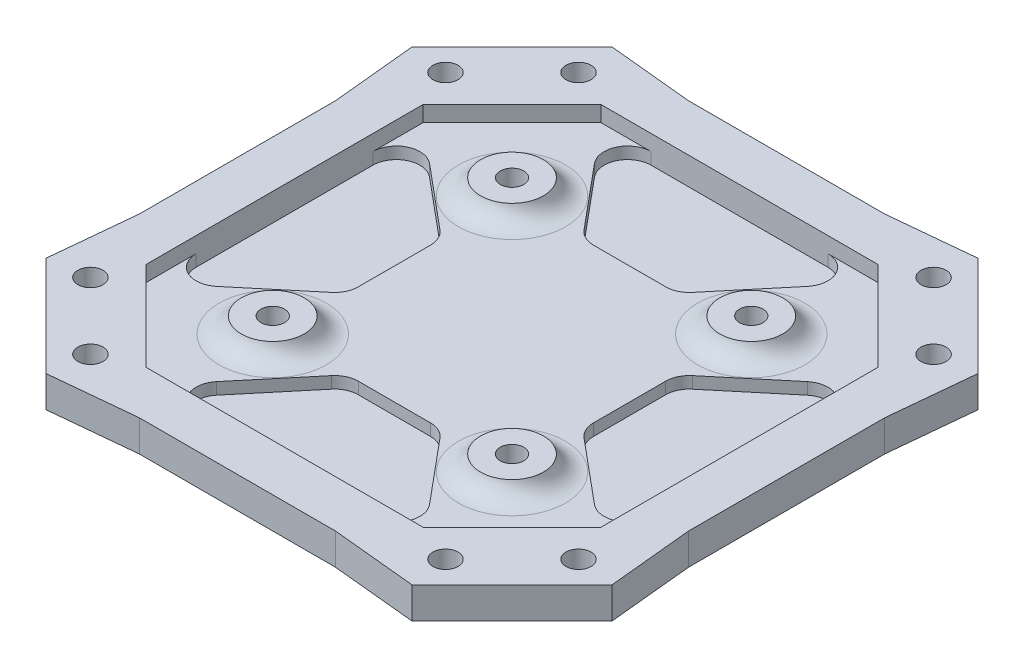
SolidWorks part; units mm, degrees
ref_plane "Front Plane" through (0, 0, 0) normal (0, 0, 1) x (1, 0, 0)
ref_plane "Top Plane" through (0, 0, 0) normal (0, 1, 0) x (1, 0, 0)
ref_plane "Right Plane" through (0, 0, 0) normal (1, 0, 0) x (0, 0, -1)
sketch "Sketch1" plane through (0, 0, 0) normal (0, 1, 0) x (1, 0, 0)
  line L0 (-12.5, 0) -> (12.5, 0)
  line L1 (12.5, 0) -> (23.338, 1.0627)
  line L2 (23.338, 1.0627) -> (36.0659, -11.6652)
  line L3 (36.0659, -11.6652) -> (35.0033, -22.5033)
  line L4 (35.0033, -22.5033) -> (35.0033, -47.5033)
  line L5 (0, 0) -> (0, -59.9756) construction
  line L6 (35.0033, -35.0033) -> (-52.1457, -35.0033) construction
  line L7 (-35.0033, -22.5033) -> (-35.0033, -47.5033)
  line L8 (-36.0659, -11.6652) -> (-35.0033, -22.5033)
  line L9 (-23.338, 1.0627) -> (-36.0659, -11.6652)
  line L10 (-12.5, 0) -> (-23.338, 1.0627)
  line L11 (0, -70.0065) -> (0, -10.0309) construction
  line L12 (-12.5, -70.0065) -> (-23.338, -71.0692)
  line L13 (-23.338, -71.0692) -> (-36.0659, -58.3413)
  line L14 (-36.0659, -58.3413) -> (-35.0033, -47.5033)
  line L15 (36.0659, -58.3413) -> (35.0033, -47.5033)
  line L16 (23.338, -71.0692) -> (36.0659, -58.3413)
  line L17 (12.5, -70.0065) -> (23.338, -71.0692)
  line L18 (-12.5, -70.0065) -> (12.5, -70.0065)
  point P17 (-35.0033, -35.0033)
  dimension "D1" = 12.5
  dimension "D2" = 10.89
  dimension "D3" = 5.6
  dimension "D4" = 18
  dimension "D5" = 50.6
  dimension "D6" = 50.6
  dimension "D7" = 10.89
  dimension "D8" = 12.5
extrude "Boss-Extrude1" add sketch "Sketch1" along normal blind 4
sketch "Sketch2" plane through (0, 4, 0) normal (0, 1, 0) x (1, 0, 0)
  line L0 (0, 0) -> (0, -70.0065) construction
  line L1 (-12.5, -70.0065) -> (12.5, -70.0065) construction
  line L2 (-35.0033, -35.0033) -> (35.0033, -35.0033) construction
  line L3 (-35.0033, -22.5033) -> (-35.0033, -47.5033) construction
  line L4 (35.0033, -47.5033) -> (35.0033, -22.5033) construction
  circle A0 centre (22.63, -3.8933) radius 1.6
  circle A1 centre (31.11, -12.3733) radius 1.6
  circle A2 centre (-31.11, -12.3733) radius 1.6
  circle A3 centre (-22.63, -3.8933) radius 1.6
  circle A4 centre (31.11, -57.6333) radius 1.6
  circle A5 centre (22.63, -66.1133) radius 1.6
  circle A6 centre (-22.63, -66.1133) radius 1.6
  circle A7 centre (-31.11, -57.6333) radius 1.6
  dimension "D1" = 3.2
  dimension "D2" = 3.2
  dimension "D3" = 22.63
  dimension "D4" = 31.11
  dimension "D5" = 31.11
  dimension "D6" = 22.63
extrude "Cut-Extrude1" cut sketch "Sketch2" against normal through all
sketch "Sketch3" plane through (0, 4, 0) normal (0, 1, 0) x (1, 0, 0)
  line L0 (-17.6728, -6) -> (17.6728, -6)
  line L1 (-29.0033, -17.3305) -> (-29.0033, -52.6761)
  line L3 (-17.6728, -64.0065) -> (17.6728, -64.0065)
  line L4 (12.5, 0) -> (-12.5, 0) construction
  line L5 (-35.0033, -22.5033) -> (-35.0033, -47.5033) construction
  line L6 (-12.5, -70.0065) -> (12.5, -70.0065) construction
  line L7 (35.0033, -47.5033) -> (35.0033, -22.5033) construction
  line L8 (-17.6728, -6) -> (-29.0033, -17.3305)
  line L9 (-23.338, 1.0627) -> (-36.0659, -11.6652) construction
  line L11 (0, 0) -> (0, -70.0065) construction
  line L12 (-35.0033, -35.0033) -> (35.0033, -35.0033) construction
  line L13 (17.6728, -6) -> (29.0033, -17.3305)
  line L14 (17.6728, -64.0065) -> (29.0033, -52.6761)
  line L15 (-17.6728, -64.0065) -> (-29.0033, -52.6761)
  line L16 (29.0033, -17.3305) -> (29.0033, -52.6761)
  dimension "D1" = 6
  dimension "D2" = 6
  dimension "D5" = 9
extrude "Cut-Extrude2" cut sketch "Sketch3" against normal blind 2
sketch "Sketch4" plane through (0, 2, 0) normal (0, 1, 0) x (1, 0, 0)
  line L0 (-4.5953, -50.0065) -> (4.5953, -50.0065)
  line L1 (-17.6728, -64.0065) -> (17.6728, -64.0065) construction
  line L3 (-17.6728, -64.0065) -> (17.6728, -64.0065) construction
  line L4 (-6.8995, -51.0854) -> (-13.5697, -59.0854)
  line L5 (-11.2655, -64.0065) -> (11.2655, -64.0065)
  line L6 (13.5697, -59.0854) -> (6.8995, -51.0854)
  line L7 (29.0033, -52.6761) -> (29.0033, -17.3305) construction
  line L8 (17.6728, -6) -> (-17.6728, -6) construction
  line L9 (-24.0821, -48.5729) -> (-16.0821, -41.9028)
  line L10 (-15.0033, -30.4079) -> (-15.0033, -39.5986)
  line L11 (-16.0821, -28.1038) -> (-24.0821, -21.4336)
  line L12 (-29.0033, -23.7378) -> (-29.0033, -46.2688)
  line L13 (-13.5697, -10.9211) -> (-6.8995, -18.9211)
  line L14 (4.5953, -20) -> (-4.5953, -20)
  line L15 (6.8995, -18.9211) -> (13.5697, -10.9211)
  line L16 (11.2655, -6) -> (-11.2655, -6)
  line L17 (24.0821, -21.4336) -> (16.0821, -28.1038)
  line L18 (15.0033, -39.5986) -> (15.0033, -30.4079)
  line L19 (16.0821, -41.9028) -> (24.0821, -48.5729)
  line L20 (29.0033, -46.2688) -> (29.0033, -23.7378)
  arc A0 (11.2655, -64.0065) -> (13.5697, -59.0854) centre (11.2655, -61.0065) ccw
  arc A1 (-13.5697, -59.0854) -> (-11.2655, -64.0065) centre (-11.2655, -61.0065) ccw
  arc A2 (-4.5953, -50.0065) -> (-6.8995, -51.0854) centre (-4.5953, -53.0065) ccw
  arc A3 (4.5953, -50.0065) -> (6.8995, -51.0854) centre (4.5953, -53.0065) cw
  arc A4 (-15.0033, -39.5986) -> (-16.0821, -41.9028) centre (-18.0033, -39.5986) cw
  arc A5 (-29.0033, -46.2688) -> (-24.0821, -48.5729) centre (-26.0033, -46.2688) ccw
  arc A6 (-15.0033, -30.4079) -> (-16.0821, -28.1038) centre (-18.0033, -30.4079) ccw
  arc A7 (-24.0821, -21.4336) -> (-29.0033, -23.7378) centre (-26.0033, -23.7378) ccw
  arc A8 (-4.5953, -20) -> (-6.8995, -18.9211) centre (-4.5953, -17) cw
  arc A9 (-11.2655, -6) -> (-13.5697, -10.9211) centre (-11.2655, -9) ccw
  arc A10 (4.5953, -20) -> (6.8995, -18.9211) centre (4.5953, -17) ccw
  arc A11 (13.5697, -10.9211) -> (11.2655, -6) centre (11.2655, -9) ccw
  arc A12 (15.0033, -30.4079) -> (16.0821, -28.1038) centre (18.0033, -30.4079) cw
  arc A13 (29.0033, -23.7378) -> (24.0821, -21.4336) centre (26.0033, -23.7378) ccw
  arc A14 (15.0033, -39.5986) -> (16.0821, -41.9028) centre (18.0033, -39.5986) ccw
  arc A15 (24.0821, -48.5729) -> (29.0033, -46.2688) centre (26.0033, -46.2688) ccw
  point P7 (0, -64.0065)
  point P8 (0, -50.0065)
  point P14 (17.6728, -64.0065)
  point P17 (-17.6728, -64.0065)
  point P20 (-6, -50.0065)
  point P23 (6, -50.0065)
  point P24 (0, -35.0033)
  point P27 (29.0033, -35.0033)
  point P31 (0, -6)
  point P69 (0, -35.0033)
  dimension "D3" = 3
  dimension "D1" = 12
  dimension "D2" = 14
  dimension "D4" = 4
extrude "Cut-Extrude3" cut sketch "Sketch4" against normal blind 1.5
sketch "Sketch5" plane through (0, 2, 0) normal (0, 1, 0) x (1, 0, 0)
  line L0 (0, 0) -> (0, -70.0065) construction
  line L1 (-12.5, -70.0065) -> (12.5, -70.0065) construction
  line L2 (-35.0033, -35.0033) -> (35.0033, -35.0033) construction
  line L3 (-35.0033, -22.5033) -> (-35.0033, -47.5033) construction
  line L4 (35.0033, -47.5033) -> (35.0033, -22.5033) construction
  circle A0 centre (15.25, -19.7533) radius 4
  circle A1 centre (-15.25, -19.7533) radius 4
  circle A2 centre (-15.25, -50.2533) radius 4
  circle A3 centre (15.25, -50.2533) radius 4
  dimension "D1" = 8
  dimension "D2" = 15.25
  dimension "D3" = 15.25
extrude "Boss-Extrude3" add sketch "Sketch5" along normal blind 2
sketch "Sketch6" plane through (0, 4, 0) normal (0, 1, 0) x (1, 0, 0)
  line L0 (-29.0033, -17.3305) -> (-29.0033, -52.6761) construction
  circle A0 centre (15.25, -19.7533) radius 1.5
  circle A1 centre (15.25, -50.2533) radius 1.5
  circle A2 centre (-15.25, -50.2533) radius 1.5
  circle A3 centre (-15.25, -19.7533) radius 1.5
  point P3 (0, -35.0033)
  point P6 (-29.0033, -35.0033)
  point P16 (0, -35.0033)
  dimension "D1" = 3
  dimension "D2" = 4
extrude "Cut-Extrude4" cut sketch "Sketch6" against normal through all
fillet "Fillet1" radius 3 4 edges at (-15.25, 2, 15.7533) (15.25, 2, 15.7533) (15.25, 2, 46.2533) (-15.25, 2, 46.2533)
